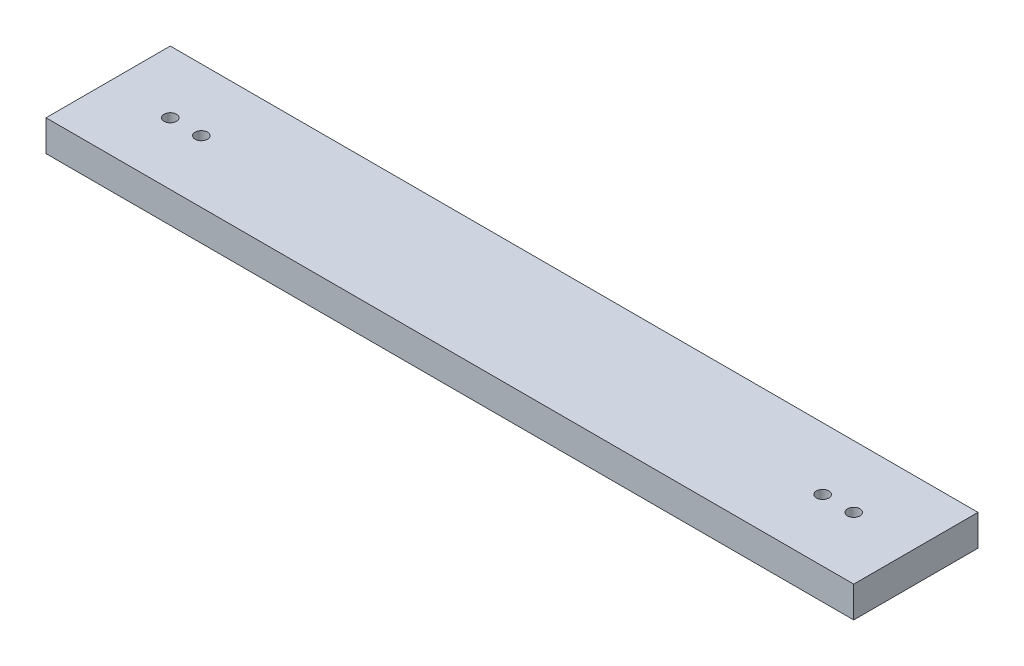
SolidWorks part; units mm, degrees
ref_plane "Front Plane" through (0, 0, 0) normal (0, 0, 1) x (1, 0, 0)
ref_plane "Top Plane" through (0, 0, 0) normal (0, 1, 0) x (1, 0, 0)
ref_plane "Right Plane" through (0, 0, 0) normal (1, 0, 0) x (0, 0, -1)
sketch "Sketch3" plane through (0, 0, 0) normal (0, 1, 0) x (1, 0, 0)
  line L1 (0, 80) -> (520, 80)
  line L2 (0, 80) -> (0, 0)
  line L3 (0, 0) -> (520, 0)
  line L4 (520, 80) -> (520, 0)
  dimension "D1" = 520
  dimension "D2" = 80
extrude "Boss-Extrude1" add sketch "Sketch3" along normal blind 20
sketch "Sketch4" plane through (0, 20, 0) normal (0, 1, 0) x (1, 0, 0)
  circle A0 centre (40, 40) radius 4
  circle A1 centre (60, 40) radius 4
  circle A2 centre (460, 40) radius 4
  circle A3 centre (480, 40) radius 4
  dimension "D1" = 2
  dimension "D2" = 2
extrude "Cut-Extrude1" cut sketch "Sketch4" against normal through all
